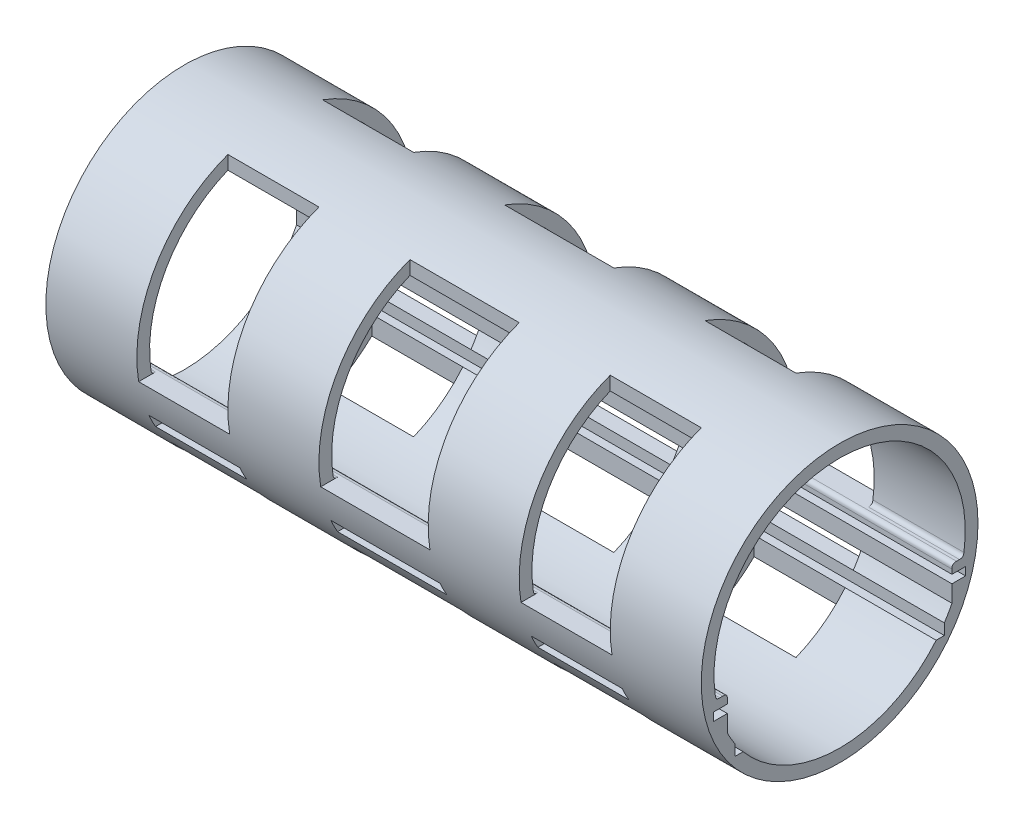
SolidWorks part; units mm, degrees
ref_plane "Front Plane" through (0, 0, 0) normal (0, 0, 1) x (1, 0, 0)
ref_plane "Top Plane" through (0, 0, 0) normal (0, 1, 0) x (1, 0, 0)
ref_plane "Right Plane" through (0, 0, 0) normal (1, 0, 0) x (0, 0, -1)
sketch "Sketch1" plane through (0, 0, 0) normal (1, 0, 0) x (0, 0, -1)
  circle A0 centre (0, 0) radius 76
  circle A1 centre (0, 0) radius 69
extrude "Boss-Extrude3" add sketch "Sketch1" along normal blind 360
sketch "Sketch2" plane through (0, 0, 0) normal (0, 1, 0) x (1, 0, 0)
  line L1 (50, 76) -> (50, 26)
  line L2 (50, 26) -> (100, 26)
  line L3 (100, 26) -> (100, 76)
  line L5 (310, 76) -> (310, 26)
  line L6 (310, 26) -> (260, 26)
  line L7 (260, 26) -> (260, 76)
  line L9 (210, 76) -> (210, 26)
  line L10 (210, 26) -> (150, 26)
  line L11 (150, 26) -> (150, 76)
  line L13 (50, 76) -> (100, 76)
  line L14 (150, 76) -> (210, 76)
  line L15 (260, 76) -> (310, 76)
  dimension "D1" = 50
  dimension "D2" = 50
  dimension "D3" = 50
  dimension "D4" = 50
  dimension "D6" = 50
  dimension "D8" = 50
extrude "Cut-Extrude1" cut sketch "Sketch2" along normal blind 125 and the other way blind 135
sketch "Sketch3" plane through (0, 0, 0) normal (0, 1, 0) x (1, 0, 0)
  line L1 (150, -76) -> (150, -26)
  line L5 (50, -76) -> (50, -26)
  line L6 (0, -76) -> (360, -76) construction
  line L7 (50, -26) -> (100, -26)
  line L8 (100, -26) -> (100, -76)
  line L9 (100, -76) -> (50, -76)
  line L10 (150, -26) -> (210, -26)
  line L11 (210, -26) -> (210, -76)
  line L12 (210, -76) -> (150, -76)
  line L14 (310, -76) -> (310, -26)
  line L15 (310, -26) -> (260, -26)
  line L16 (260, -26) -> (260, -76)
  line L17 (260, -76) -> (310, -76)
  line L18 (0, 76) -> (0, -76) construction
  line L19 (360, -76) -> (360, 76) construction
  dimension "D1" = 50
  dimension "D2" = 60
  dimension "D3" = 50
  dimension "D4" = 50
  dimension "D5" = 50
  dimension "D6" = 50
  dimension "D7" = 50
extrude "Cut-Extrude3" cut sketch "Sketch3" along normal blind 196 and the other way blind 244
sketch "Sketch4" plane through (0, 0, 0) normal (-1, 0, 0) x (0, 0, 1)
  line L8 (-57.5, -44.1588) -> (57.5, -44.1588)
  line L12 (-52.5, -41.6588) -> (-2.5, -41.6588)
  line L14 (69.1892, -17.1588) -> (69.1892, -21.6588)
  line L15 (69.1892, -21.6588) -> (57.5, -21.6588)
  line L18 (-69.1892, -21.6588) -> (-72.5294, -22.7044)
  line L26 (57.5, -44.1588) -> (57.5, -21.6588)
  line L28 (-57.5, -44.1588) -> (-60.2759, -46.2906)
  line L29 (-69.1892, -17.1588) -> (69.1892, -17.1588)
  line L30 (57.5, -44.1588) -> (60.2759, -46.2906)
  line L31 (69.1892, -21.6588) -> (72.5294, -22.7044)
  line L32 (-57.5, -44.1588) -> (-57.5, -21.6588)
  line L36 (-69.1892, -21.6588) -> (-57.5, -21.6588)
  line L37 (-69.1892, -17.1588) -> (-69.1892, -21.6588)
  line L38 (-52.5, -17.1588) -> (-2.5, -17.1588)
  line L41 (2.5, -17.1588) -> (52.5, -17.1588)
  line L43 (-2.5, -41.6588) -> (-2.5, -17.1588)
  line L44 (2.5, -17.1588) -> (2.5, -41.6588)
  line L45 (52.5, -41.6588) -> (52.5, -17.1588)
  line L46 (-52.5, -17.1588) -> (-52.5, -41.6588)
  line L47 (2.5, -41.6588) -> (52.5, -41.6588)
  circle A0 centre (0, 0) radius 76 construction
  point P6 (0, -44.1588)
  point P12 (0, -17.1588)
  point P31 (0, -41.6588)
  circle M53 centre (0, 0) radius 69
  dimension "D2" = 5
  dimension "D3" = 5
  dimension "D4" = 115
  dimension "D5" = 3.5
  dimension "D6" = 3.5
  dimension "D7" = 3.5
  dimension "D8" = 3.5
  dimension "D9" = 22.5
  dimension "D10" = 22.5
  dimension "D11" = 5
  dimension "D12" = 24.5
  dimension "D13" = 138.3784
  dimension "D14" = 4.5
  dimension "D15" = 24.5
  dimension "D16" = 50
  dimension "D17" = 50
  dimension "D18" = 11.6892
  dimension "D19" = 11.6892
  dimension "D20" = 27
extrude "Cut-Extrude4" cut sketch "Sketch4" against normal blind 404 contours L29 L37 L36 M53 | L32 L8 M53 | L8 L26 M53 | L29 L15 L14 M53 region at (0, -42.1914, -56.0344) region at (0, -42.1914, 56.0344) region at (0, -19.5744, -67.6704) region at (0, -19.5744, 67.6704)
sketch "Sketch5" plane through (0, 0, 0) normal (-1, 0, 0) x (0, 0, 1)
  line L0 (-65.5126, -21.6588) -> (-69.1892, -21.6588)
  line L1 (-69.1892, -21.6588) -> (-69.1892, -17.1588)
  line L2 (-69.1892, -17.1588) -> (-61.6892, -17.1588)
  line L3 (-65.5126, -21.6588) -> (-61.6892, -21.6588)
  line L4 (-61.6892, -21.6588) -> (-61.6892, -30.9102)
  line L5 (-61.6892, -30.9102) -> (-69.4302, -30.9102)
  line L6 (-61.6892, -17.1588) -> (-61.6892, -12.1588)
  line L7 (-61.6892, -12.1588) -> (-67.9203, -12.1588)
  line L8 (-67.9203, -12.1588) -> (-75.0211, -12.1588)
  line L9 (61.6892, -30.9102) -> (69.4302, -30.9102)
  line L10 (-57.5, -38.1412) -> (-65.7362, -38.1412)
  line L11 (-53.0189, -44.1588) -> (-53.0189, -54.4518)
  line L12 (67.9203, -12.1588) -> (75.0211, -12.1588)
  line L13 (57.5, -38.1412) -> (57.5, -44.1588)
  line L15 (61.6892, -12.1588) -> (67.9203, -12.1588)
  line L16 (61.6892, -17.1588) -> (61.6892, -12.1588)
  line L18 (61.6892, -21.6588) -> (61.6892, -30.9102)
  line L19 (65.5126, -21.6588) -> (61.6892, -21.6588)
  line L20 (69.1892, -17.1588) -> (61.6892, -17.1588)
  line L21 (69.1892, -21.6588) -> (69.1892, -17.1588)
  line L22 (65.5126, -21.6588) -> (69.1892, -21.6588)
  line L23 (57.5, -44.1588) -> (53.0189, -44.1588)
  line L24 (53.0189, -44.1588) -> (53.0189, -49.1588)
  line L25 (53.0189, -49.1588) -> (57.9604, -49.1588)
  line L26 (57.5, -38.1412) -> (65.7362, -38.1412)
  line L27 (-57.5, -38.1412) -> (-57.5, -44.1588)
  line L28 (-57.5, -44.1588) -> (-53.0189, -44.1588)
  arc A0 (-65.5126, -21.6588) -> (-57.5, -38.1412) centre (0, 0) ccw construction
  circle A1 centre (0, 0) radius 76 construction
  arc A2 (66.8324, -17.1588) -> (-66.8324, -17.1588) centre (0, 0) ccw construction
  arc A3 (75.0211, -12.1588) -> (69.4302, -30.9102) centre (0, 0) cw
  arc A4 (65.7362, -38.1412) -> (57.9604, -49.1588) centre (0, 0) cw
  arc A5 (-65.7362, -38.1412) -> (-53.0189, -54.4518) centre (0, 0) ccw
  arc A6 (-75.0211, -12.1588) -> (-69.4302, -30.9102) centre (0, 0) ccw
extrude "Boss-Extrude5" add sketch "Sketch5" against normal blind 360
fillet "Fillet1" radius 2.5 10 edges at (25, -12.1588, 67.9203) (125, -12.1588, 67.9203) (235, -12.1588, 67.9203) (335, -12.1588, 67.9203) (335, -12.1588, -67.9203) (235, -12.1588, -67.9203) (125, -12.1588, -67.9203) (25, -12.1588, -67.9203) (180, -12.1588, -61.6892) (180, -12.1588, 61.6892) curvature continuous yes
